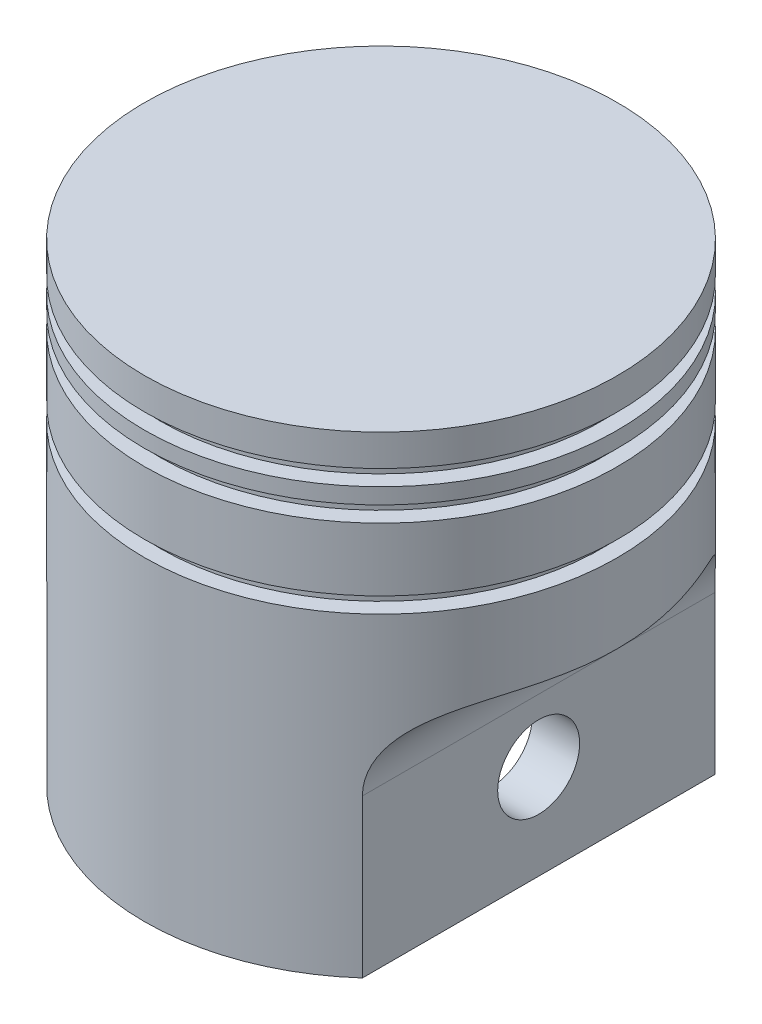
SolidWorks part; units mm, degrees
ref_plane "정면" through (0, 0, 0) normal (0, 0, 1) x (1, 0, 0)
ref_plane "윗면" through (0, 0, 0) normal (0, 1, 0) x (1, 0, 0)
ref_plane "우측면" through (0, 0, 0) normal (1, 0, 0) x (0, 0, -1)
sketch "Sketch1" plane through (0, 0, 0) normal (0, 1, 0) x (1, 0, 0)
  circle A0 centre (0, 0) radius 15
  dimension "D1" = 30
extrude "Boss-Extrude1" add sketch "Sketch1" along normal blind 30
sketch "Sketch5" plane through (0, 0, 0) normal (0, 0, 1) x (1, 0, 0)
  line L0 (-10, 0) -> (-10, 15)
  line L1 (-15, 0) -> (15, 0) construction
  line L2 (-10, 15) -> (-15, 15)
  line L3 (-15, 30) -> (-15, 0) construction
  line L4 (-15, 15) -> (-15, 0)
  line L5 (-15, 0) -> (-10, 0)
  line L6 (15, 0) -> (10, 0)
  line L7 (10, 0) -> (10, 15)
  line L8 (10, 15) -> (15, 15)
  line L9 (15, 0) -> (15, 30) construction
  line L10 (15, 15) -> (15, 0)
  dimension "D1" = 5
  dimension "D2" = 5
  dimension "D3" = 15
  dimension "D4" = 15
extrude "Cut-Extrude3" cut sketch "Sketch5" against normal through all both and the other way through all
sketch "Sketch6" plane through (0, 30, 0) normal (0, 1, 0) x (1, 0, 0)
  circle A0 centre (0, 0) radius 14
  circle A1 centre (0, 0) radius 15
  dimension "D1" = 28
extrude "Cut-Extrude5" cut sketch "Sketch6" against normal blind 10 contours A1
extrude "Boss-Extrude2" add sketch "Sketch6<4>" against normal blind 10 contours A0 region at (0, 30, 0)
sketch "Sketch6<4>" plane through (0, 30, 0) normal (0, 1, 0) x (1, 0, 0) same geometry as "Sketch6"
extrude "Boss-Extrude3" add sketch "Sketch6<5>" against normal blind 9
sketch "Sketch6<5>" plane through (0, 30, 0) normal (0, 1, 0) x (1, 0, 0) same geometry as "Sketch6"
extrude "Cut-Extrude6" cut sketch "Sketch6<6>" against normal blind 5
sketch "Sketch6<6>" plane through (0, 30, 0) normal (0, 1, 0) x (1, 0, 0) same geometry as "Sketch6"
extrude "Boss-Extrude4" add sketch "Sketch6<7>" against normal blind 4
sketch "Sketch6<7>" plane through (0, 30, 0) normal (0, 1, 0) x (1, 0, 0) same geometry as "Sketch6"
extrude "Cut-Extrude7" cut sketch "Sketch6<8>" against normal blind 3
sketch "Sketch6<8>" plane through (0, 30, 0) normal (0, 1, 0) x (1, 0, 0) same geometry as "Sketch6"
extrude "Boss-Extrude5" add sketch "Sketch6<9>" against normal blind 2
sketch "Sketch6<9>" plane through (0, 30, 0) normal (0, 1, 0) x (1, 0, 0) same geometry as "Sketch6"
shell "Shell2" thickness 3 removed face at (0, 0, 0)
sketch "Sketch4" plane through (0, 0, 0) normal (1, 0, 0) x (0, 0, -1)
  line L1 (11.1803, 0) -> (-11.1803, 0) construction
  circle A0 centre (0, 6) radius 2.6
  dimension "D1" = 5.2
  dimension "D2" = 6
extrude "Cut-Extrude2" cut sketch "Sketch4" against normal through all both and the other way through all
fillet "Fillet1" radius 5 2 edges at (10, 15, 0) (-10, 15, 0)
